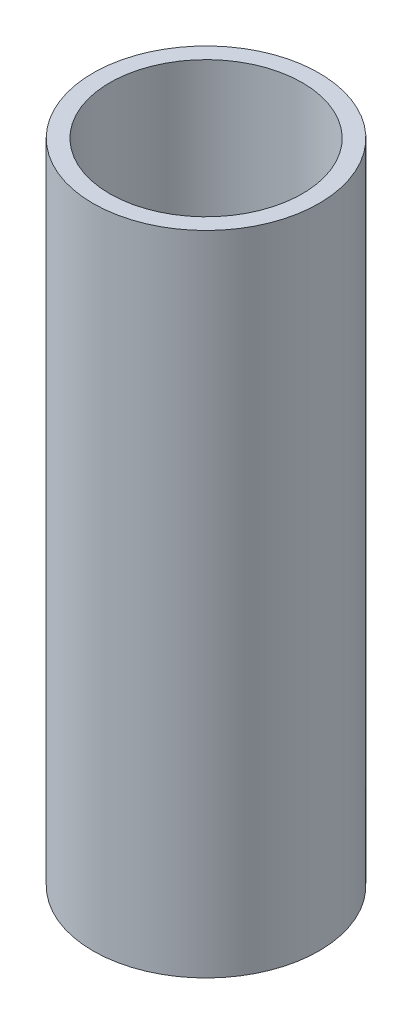
SolidWorks part; units mm, degrees
ref_plane "Front Plane" through (0, 0, 0) normal (0, 0, 1) x (1, 0, 0)
ref_plane "Top Plane" through (0, 0, 0) normal (0, 1, 0) x (1, 0, 0)
ref_plane "Right Plane" through (0, 0, 0) normal (1, 0, 0) x (0, 0, -1)
sketch "Sketch1" plane through (0, 0, 0) normal (0, 1, 0) x (1, 0, 0)
  circle A0 centre (0, 0) radius 25
  dimension "SLEEVE_OD" = 50
extrude "Boss-Extrude1" add sketch "Sketch1" along normal blind 143.1929
sketch "Sketch2" plane through (0, 0, 0) normal (0, 1, 0) x (1, 0, 0)
  circle A0 centre (0, 0) radius 21.2967
  dimension "BORE_D" = 42.5934
extrude "Cut-Extrude1" cut sketch "Sketch2" along normal through all
chamfer "Chamfer1" distance 2.323 angle 45 rebuild error yes
